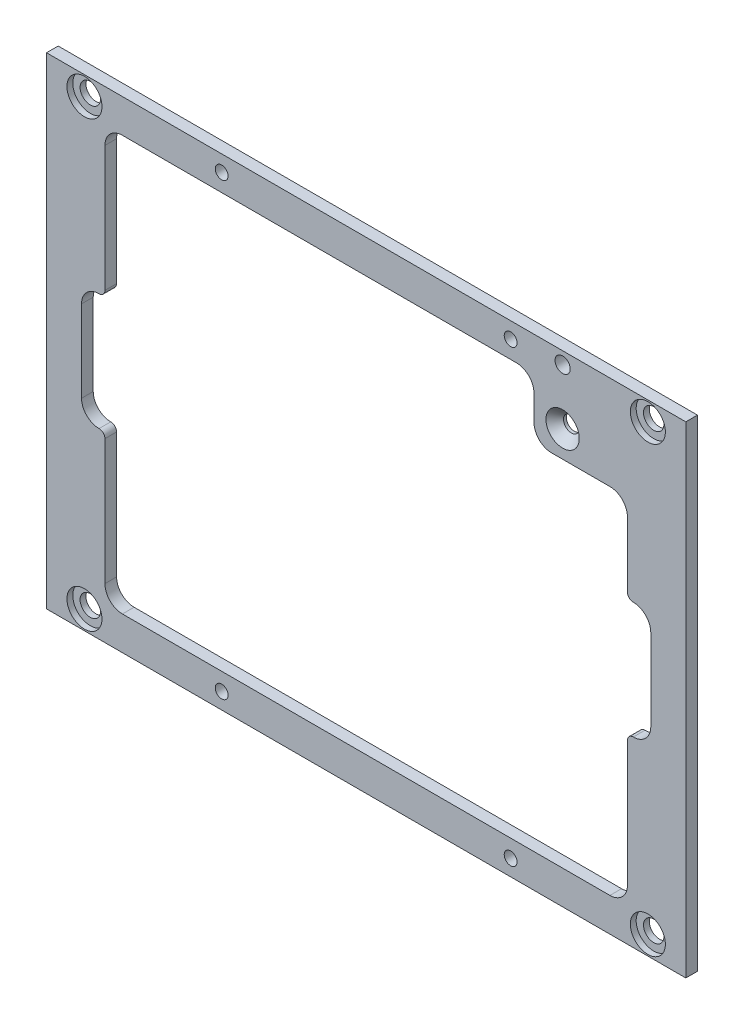
SolidWorks part; units mm, degrees
ref_plane "Front Plane" through (0, 0, 0) normal (0, 0, 1) x (1, 0, 0)
ref_plane "Top Plane" through (0, 0, 0) normal (0, 1, 0) x (1, 0, 0)
ref_plane "Right Plane" through (0, 0, 0) normal (1, 0, 0) x (0, 0, -1)
sketch "Sketch1" plane through (0, 0, 0) normal (0, 0, 1) x (1, 0, 0)
  line L0 (55.75, -83) -> (-55.75, -83) construction
  line L1 (-54.75, -0.5) -> (54.75, -0.5)
  line L2 (-54.75, -0.5) -> (-54.75, -83)
  line L3 (-54.75, -83) -> (54.75, -83)
  line L4 (54.75, -0.5) -> (54.75, -83)
  line L5 (-54.75, -41.75) -> (54.75, -41.75) construction
  line L6 (28.75, -9.25) -> (28.75, -13.6)
  line L7 (-41.75, -6.25) -> (25.75, -6.25)
  line L8 (-44.75, -9.25) -> (-44.75, -31.75)
  line L9 (-41.75, -77.25) -> (41.75, -77.25)
  line L10 (44.75, -19.6) -> (44.75, -31.75)
  line L11 (31.75, -16.6) -> (41.75, -16.6)
  line L12 (54.75, -41.75) -> (48.75, -41.75) construction
  line L13 (48.75, -41.75) -> (48.75, -51.75)
  line L14 (44.75, -31.75) -> (48.75, -31.75)
  line L15 (-44.75, -31.75) -> (-48.75, -31.75)
  line L16 (44.75, -51.75) -> (48.75, -51.75)
  line L17 (48.75, -31.75) -> (48.75, -41.75)
  line L18 (44.75, -51.75) -> (44.75, -74.25)
  line L19 (-48.75, -31.75) -> (-48.75, -51.75)
  line L20 (-48.75, -51.75) -> (-44.75, -51.75)
  line L21 (-44.75, -51.75) -> (-44.75, -74.25)
  arc A0 (41.75, -77.25) -> (44.75, -74.25) centre (41.75, -74.25) ccw
  arc A1 (-44.75, -74.25) -> (-41.75, -77.25) centre (-41.75, -74.25) ccw
  arc A2 (-41.75, -6.25) -> (-44.75, -9.25) centre (-41.75, -9.25) ccw
  arc A3 (28.75, -9.25) -> (25.75, -6.25) centre (25.75, -9.25) ccw
  arc A4 (41.75, -16.6) -> (44.75, -19.6) centre (41.75, -19.6) cw
  arc A5 (28.75, -13.6) -> (31.75, -16.6) centre (31.75, -13.6) ccw
  point P4 (-54.75, -41.75)
  point P24 (28.75, -6.25)
  point P29 (28.75, -16.6)
  dimension "D6" = 3
  dimension "D8" = 3
  dimension "D2" = 109.5
  dimension "D3" = 10
  dimension "D4" = 71
  dimension "D5" = 35.5
  dimension "D7" = 73.5
  dimension "D9" = 16.1
  dimension "D10" = 4
  dimension "D11" = 10
  dimension "D12" = 10
  dimension "D13" = 89.5
  dimension "D14" = 82.5
  dimension "D15" = 10
  dimension "D16" = 10
  dimension "D17" = 4
extrude "Boss-Extrude1" add sketch "Sketch1" along normal blind 2
hole_wizard "Ø3.5 (3.5) Diameter Hole1" positions "Sketch4" profile "Sketch3" hole size "Ø3.5" standard "Ansi Metric" end condition up to next
sketch "Sketch4" plane through (0, 0, 2) normal (0, 0, 1) x (1, 0, 0)
  line L0 (-54.75, -0.5) -> (-54.75, -83) construction
  line L3 (54.75, -83) -> (54.75, -0.5) construction
  line L4 (-54.75, -41.75) -> (54.75, -41.75) construction
  point P0 (-48.25, -3.75)
  point P1 (-48.25, -79.75)
  point P3 (48.25, -79.75)
  point P5 (48.25, -3.75)
  dimension "D1" = 6.5
  dimension "D2" = 38
  dimension "D3" = 6.5
  dimension "D4" = 38
  dimension "D5" = 38
  dimension "D6" = 6.5
  dimension "D7" = 6.5
  dimension "D8" = 38
sketch "Sketch3" plane through (-48.25, -3.75, 2) normal (1, 0, 0) x (0, -1, 0)
  line L0 (0, 0) -> (0, 2)
  line L1 (0, 2) -> (1.75, 2)
  line L2 (1.75, 2) -> (1.75, 0)
  line L5 (1.75, 0) -> (0, 0)
  line L11 (0, -6.35) -> (0, 107.95) construction
  dimension "Thru Hole Dia." = 3.5
  dimension "Thru Hole Depth" = 2
hole_wizard "CSK for M2.5 Flat Countersunk Head Screw1" positions "Sketch6" profile "Sketch5" countersink size "M2.5" standard "JIS" end condition up to next
sketch "Sketch6" plane through (0, 0, 2) normal (0, 0, 1) x (1, 0, 0)
  line L1 (41.75, -16.6) -> (31.75, -16.6) construction
  line L2 (54.75, -83) -> (54.75, -0.5) construction
  point P0 (33.65, -12.1)
  dimension "D1" = 21.1
  dimension "D2" = 4.5
sketch "Sketch5" plane through (33.65, -12.1, 2) normal (1, 0, 0) x (0, -1, 0)
  line L0 (0, 0) -> (0, 2)
  line L1 (0, 2) -> (1.35, 2)
  line L2 (1.35, 2) -> (1.35, 1.5)
  line L3 (1.35, 1.5) -> (2.85, 0)
  line L5 (2.85, 0) -> (0, 0)
  line L6 (-1.35, 1.5) -> (-2.85, 0) construction
  line L11 (0, -6.35) -> (0, 107.95) construction
  dimension "Thru Hole Dia." = 2.7
  dimension "Thru Hole Depth" = 2
  dimension "Near C'Sink Dia." = 5.7
  dimension "Near C'Sink Angle" = 90
hole_wizard "Ø2.6 (2.6) Diameter Hole1" positions "Sketch8" profile "Sketch7" hole size "Ø2.6" standard "Ansi Metric" end condition up to next
sketch "Sketch8" plane through (0, 0, 2) normal (0, 0, 1) x (1, 0, 0)
  line L1 (54.75, -83) -> (54.75, -0.5) construction
  circle A0 centre (33.65, -12.1) radius 1.35 construction
  point P0 (33.65, -2.57)
  dimension "D2" = 9.53
  dimension "D1" = 21.1
sketch "Sketch7" plane through (33.65, -2.57, 2) normal (1, 0, 0) x (0, -1, 0)
  line L0 (0, 0) -> (0, 2)
  line L1 (0, 2) -> (1.3, 2)
  line L2 (1.3, 2) -> (1.3, 0)
  line L5 (1.3, 0) -> (0, 0)
  line L11 (0, -6.35) -> (0, 107.95) construction
  dimension "Thru Hole Dia." = 2.6
  dimension "Thru Hole Depth" = 2
sketch "Sketch9" plane through (0, 0, 2) normal (0, 0, 1) x (1, 0, 0)
  circle A0 centre (-48.25, -3.75) radius 3
  circle A1 centre (48.25, -3.75) radius 3
  circle A2 centre (48.25, -79.75) radius 3
  circle A3 centre (-48.25, -79.75) radius 3
  dimension "D1" = 6
  dimension "D2" = 6
  dimension "D3" = 6
  dimension "D4" = 6
extrude "Cut-Extrude1" cut sketch "Sketch9" against normal blind 1
hole_wizard "Ø2.2 (2.2) Diameter Hole1" positions "Sketch11" profile "Sketch10" hole size "Ø2.2" standard "Ansi Metric" end condition up to next
sketch "Sketch11" plane through (0, 0, 2) normal (0, 0, 1) x (1, 0, 0)
  line L0 (-54.75, -0.5) -> (-54.75, -83) construction
  line L2 (54.75, -83) -> (54.75, -0.5) construction
  line L4 (-54.75, -41.75) -> (54.75, -41.75) construction
  point P0 (-24.75, -3.25)
  point P1 (24.75, -3.25)
  point P3 (-24.75, -80.25)
  point P5 (24.75, -80.25)
  dimension "D1" = 30
  dimension "D2" = 38.5
  dimension "D3" = 30
  dimension "D4" = 38.5
  dimension "D5" = 38.5
  dimension "D6" = 30
  dimension "D7" = 30
  dimension "D8" = 38.5
sketch "Sketch10" plane through (-24.75, -3.25, 2) normal (1, 0, 0) x (0, -1, 0)
  line L0 (0, 0) -> (0, 2)
  line L1 (0, 2) -> (1.1, 2)
  line L2 (1.1, 2) -> (1.1, 0)
  line L5 (1.1, 0) -> (0, 0)
  line L11 (0, -6.35) -> (0, 107.95) construction
  dimension "Thru Hole Dia." = 2.2
  dimension "Thru Hole Depth" = 2
fillet "Fillet1" radius 1 4 edges at (44.75, -51.75, 1) (44.75, -31.75, 1) (-44.75, -51.75, 1) (-44.75, -31.75, 1)
fillet "Fillet2" radius 3 4 edges at (48.75, -31.75, 1) (48.75, -51.75, 1) (-48.75, -51.75, 1) (-48.75, -31.75, 1)
